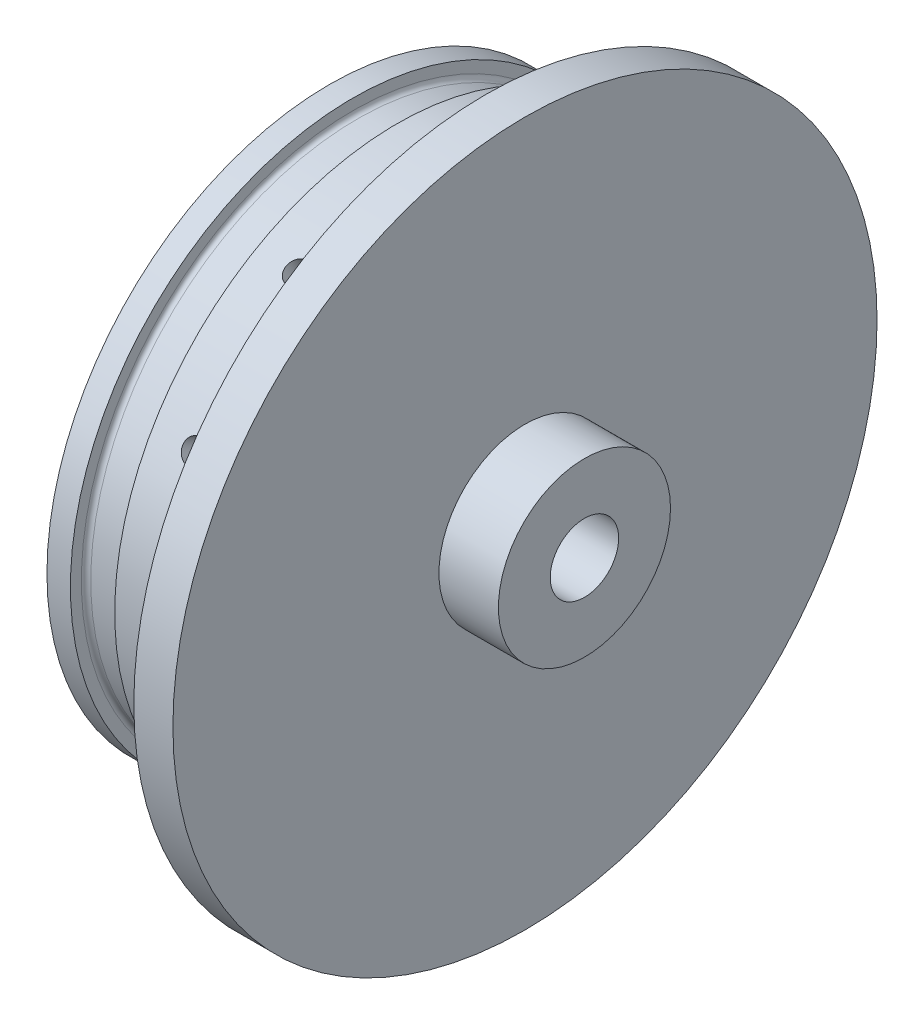
SolidWorks part; units mm, degrees
material "7075-T6 (SN)"
ref_plane "Front Plane" through (0, 0, 0) normal (0, 0, 1) x (1, 0, 0)
ref_plane "Top Plane" through (0, 0, 0) normal (0, 1, 0) x (1, 0, 0)
ref_plane "Right Plane" through (0, 0, 0) normal (1, 0, 0) x (0, 0, -1)
sketch "Sketch1" plane through (0, 0, 0) normal (1, 0, 0) x (0, 0, -1)
  circle A0 centre (0, 0) radius 57.15
  dimension "D1" = 114.3
extrude "Boss-Extrude1" add sketch "Sketch1" along normal blind 6.35
sketch "Sketch2" plane through (0, 0, 0) normal (-1, 0, 0) x (0, 0, 1)
  circle A0 centre (0, 0) radius 45.847
  dimension "D1" = 91.694
extrude "Boss-Extrude2" add sketch "Sketch2" along normal blind 25.4
sketch "Sketch10" plane through (0, 0, 0) normal (0, 1, 0) x (1, 0, 0)
  line L0 (0, 0) -> (-53.2238, 0) construction
  line L1 (-26.2636, 0) -> (26.2636, 0) construction
  line L2 (0, 0) -> (0, 64.5447) construction
  line L3 (0, -62.865) -> (0, 62.865) construction
ref_plane "Plane1" through (0, 0, -45.847) normal (0, 0, -1) x (-1, 0, 0)
sketch "Sketch11" plane through (0, 0, -45.847) normal (0, 0, -1) x (-1, 0, 0)
  line L0 (0, 0) -> (53.2238, 0) construction
  line L1 (0, -45.847) -> (0, 45.847) construction
  circle A0 centre (7.62, 0) radius 1.8986
  dimension "D2" = 3.7973
  dimension "D1" = 7.62
extrude "Cut-Extrude3" cut sketch "Sketch11" against normal blind 10.16
pattern_circular "CirPattern1" count 12 over 360 about axis through (0, 0, 0) along (-1, 0, 0) of "Cut-Extrude3" reverse direction yes
sketch "Sketch15" plane through (6.35, 0, 0) normal (1, 0, 0) x (0, 0, -1)
  circle A0 centre (0, 0) radius 5.5562
  dimension "D1" = 11.1125
extrude "Cut-Extrude4" cut sketch "Sketch15" against normal through all both and the other way through all
sketch "Sketch16" plane through (0, 0, 0) normal (0, 0, 1) x (1, 0, 0)
  line L0 (-9.5186, 45.847) -> (-25.4, 45.847) construction
  line L1 (-21.59, 45.847) -> (-14.4018, 45.847)
  line L2 (-21.59, 45.847) -> (-21.59, 44.069)
  line L3 (-20.828, 43.307) -> (-15.1638, 43.307)
  line L4 (-14.4018, 45.847) -> (-14.4018, 44.069)
  line L5 (0, 0) -> (-53.2238, 0) construction
  line L6 (-25.4, 45.847) -> (-25.4, -45.847) construction
  arc A0 (-14.4018, 44.069) -> (-15.1638, 43.307) centre (-15.1638, 44.069) cw
  arc A1 (-20.828, 43.307) -> (-21.59, 44.069) centre (-20.828, 44.069) cw
  point P8 (-26.6119, 0)
  point P13 (-14.4018, 43.307)
  point P16 (-21.59, 43.307)
  dimension "D4" = 0.762
  dimension "D1" = 43.307
  dimension "D2" = 3.81
  dimension "D3" = 7.1882
revolve "Cut-Revolve1" cut sketch "Sketch16" angle 360 about L0
sketch "Sketch17" plane through (6.35, 0, 0) normal (1, 0, 0) x (0, 0, -1)
  circle A0 centre (0, 0) radius 13.97
  circle A1 centre (0, 0) radius 5.5562
  dimension "D1" = 27.94
  dimension "D2" = 11.1125
extrude "Boss-Extrude3" add sketch "Sketch17" along normal blind 9.652
cosmetic thread "Cosmetic Thread1" parameters "D2"=23.1953
sketch "Sketch18" plane through (-25.4, 0, 0) normal (-1, 0, 0) x (0, 0, 1)
  circle A0 centre (0, 0) radius 38.1
  dimension "D1" = 76.2
extrude "Cut-Extrude5" cut sketch "Sketch18" against normal blind 6.604
sketch "Sketch19" plane through (-18.796, 0, 0) normal (-1, 0, 0) x (0, 0, 1)
  line L0 (0, 0) -> (0, 57.15) construction
  circle A0 centre (0, 0) radius 57.15 construction
  circle A1 centre (0, 33.274) radius 1.1303
  circle A2 centre (23.5283, 23.5283) radius 1.1303
  circle A3 centre (33.274, 0) radius 1.1303
  circle A4 centre (23.5283, -23.5283) radius 1.1303
  circle A5 centre (0, -33.274) radius 1.1303
  circle A6 centre (-23.5283, -23.5283) radius 1.1303
  circle A7 centre (-33.274, 0) radius 1.1303
  circle A8 centre (-23.5283, 23.5283) radius 1.1303
  point P24 (0, 0)
  dimension "D2" = 2.2606
  dimension "D1" = 33.274
  dimension "D3" = 8
extrude "Cut-Extrude6" cut sketch "Sketch19" against normal blind 6.35
sketch "Sketch20" plane through (-18.796, 0, 0) normal (-1, 0, 0) x (0, 0, 1)
  circle A0 centre (0, 0) radius 23.495
  dimension "D1" = 46.99
extrude "Cut-Extrude7" cut sketch "Sketch20" against normal blind 19.05
fillet "Fillet1" radius 2.54 1 edges at (0.254, 0, 23.495)
chamfer "Chamfer1" distance 5.08 angle 45 1 edges at (0.254, 0, 5.5562)
